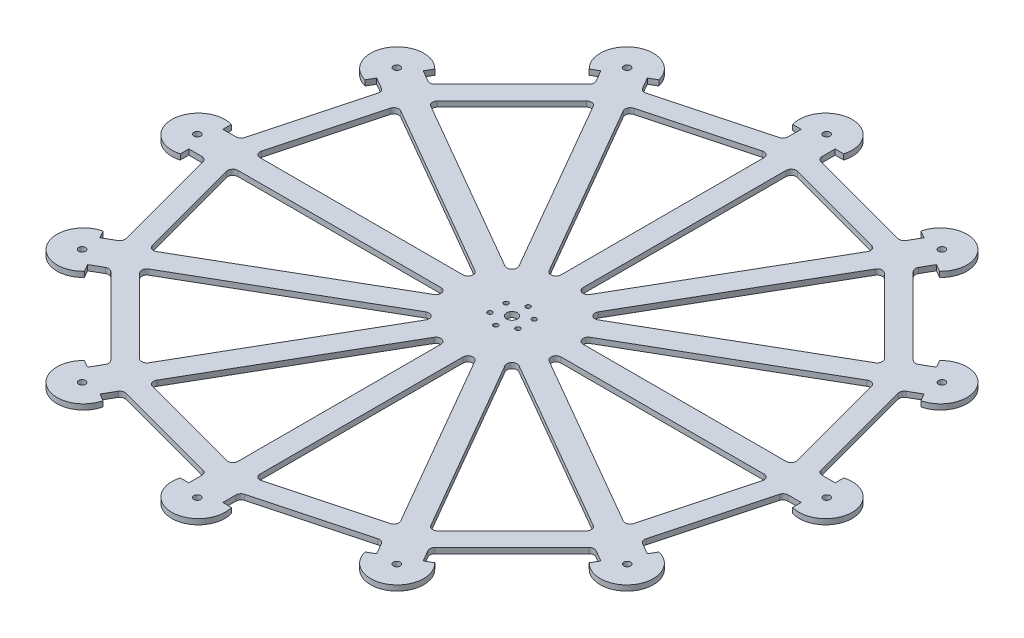
SolidWorks part; units mm, degrees
material "Balsa"
ref_plane "Front Plane" through (0, 0, 0) normal (0, 0, 1) x (1, 0, 0)
ref_plane "Top Plane" through (0, 0, 0) normal (0, 1, 0) x (1, 0, 0)
ref_plane "Right Plane" through (0, 0, 0) normal (1, 0, 0) x (0, 0, -1)
sketch "Sketch1" plane through (0, 0, 0) normal (0, 1, 0) x (1, 0, 0)
  line L0 (0, 0) -> (0, 200)
  line L1 (15, 180) -> (10, 180)
  line L2 (10, 180) -> (10, 170)
  line L3 (10, 170) -> (43.1699, 161.1122)
  line L4 (0, 0) -> (36.1011, 134.7312) construction
  line L5 (43.1699, 161.1122) -> (40.064, 149.521)
  line L6 (40.064, 149.521) -> (6.4705, 158.5224)
  line L7 (6.4705, 158.5224) -> (6.4705, 24.1481)
  line L8 (6.4705, 24.1481) -> (0, 0)
  arc A1 (0, 200) -> (15, 180) centre (0, 184.375) cw
  dimension "D3" = 5
  dimension "D1" = 15
  dimension "D2" = 15
  dimension "D4" = 10
  dimension "D5" = 20
  dimension "D6" = 200
  dimension "D7" = 25
  dimension "D8" = 12
extrude "Boss-Extrude1" add sketch "Sketch1" along normal blind 3.18
mirror "Mirror1" about plane through (43.1699, 3.18, -161.1122) normal (-0.9659, 0, -0.2588) of "Boss-Extrude1"
fillet "Fillet1" radius 3 5 edges at (6.4705, 1.59, -24.1481) (73.6576, 1.59, -140.5197) (6.4705, 1.59, -158.5224) (76.3397, 1.59, -152.2243) (10, 1.59, -170)
ref_axis "Axis1" through (0, 3.18, 0) along (0, -1, 0)
pattern_circular "CirPattern27" count 12 over 360 about axis through (0, 3.18, 0) along (0, -1, 0) of bodies 102
combine bodies "Combine1" bodies to combine 110 111 112 113 102 103 104 105 106 107 108 109
sketch "Sketch3" plane through (0, 3.18, 0) normal (0, 1, 0) x (1, 0, 0)
  circle A0 centre (0, 0) radius 3.175
  dimension "D1" = 6.35
extrude "Cut-Extrude1" cut sketch "Sketch3" against normal through all
sketch "Sketch4" plane through (0, 3.18, 0) normal (0, 1, 0) x (1, 0, 0)
  line L0 (0, 0) -> (0, 15.97) construction
  circle A0 centre (0, 9.5) radius 1.35
  circle A1 centre (8.2272, 4.75) radius 1.35
  circle A2 centre (8.2272, -4.75) radius 1.35
  circle A3 centre (0, -9.5) radius 1.35
  circle A4 centre (-8.2272, -4.75) radius 1.35
  circle A5 centre (-8.2272, 4.75) radius 1.35
  point P19 (0, 0)
  dimension "D1" = 2.7
  dimension "9.5" = 9.5
  dimension "D2" = 6
extrude "Cut-Extrude2" cut sketch "Sketch4" against normal through all
sketch "Sketch5" plane through (0, 3.18, 0) normal (0, 1, 0) x (1, 0, 0)
  line L0 (0, 0) -> (0, 115.9813) construction
  circle A0 centre (0, 185) radius 2
  dimension "D1" = 4
  dimension "D2" = 185
extrude "Cut-Extrude3" cut sketch "Sketch5" against normal through all
pattern_circular "CirPattern28" count 12 every 30 about axis through (0, 3.18, 0) along (0, -1, 0) of "Cut-Extrude3"
sketch "Sketch7" plane through (0, 3.18, 0) normal (0, 1, 0) x (1, 0, 0)
  line L0 (0, 0) -> (-157.5, 0) construction
  circle A0 centre (-157.5, 0) radius 1.6
  dimension "D2" = 3.2
  dimension "D1" = 157.5
